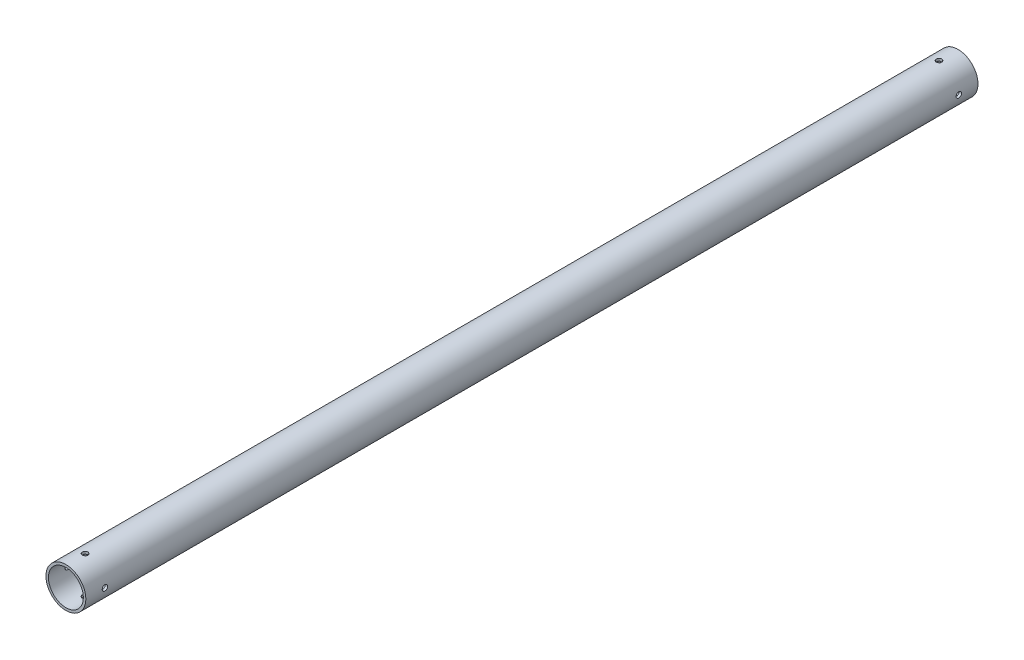
SolidWorks part; units mm, degrees
material "PC High Viscosity"
ref_plane "Front Plane" through (0, 0, 0) normal (0, 0, 1) x (1, 0, 0)
ref_plane "Top Plane" through (0, 0, 0) normal (0, 1, 0) x (1, 0, 0)
ref_plane "Right Plane" through (0, 0, 0) normal (1, 0, 0) x (0, 0, -1)
sketch "Sketch2" plane through (0, 0, 0) normal (0, 0, 1) x (1, 0, 0)
  circle A0 centre (0, 0) radius 11.1125
  circle A1 centre (0, 0) radius 12.7
  dimension "D1" = 25.4
  dimension "D2" = 1.5875
extrude "Boss-Extrude1" add sketch "Sketch2" along normal mid plane 568.4738
sketch "Sketch3" plane through (0, 0, 0) normal (0, 1, 0) x (1, 0, 0)
  line L0 (-12.7, -284.2369) -> (12.7, -284.2369) construction
  line L1 (-55, 0) -> (55, 0) construction
  circle A0 centre (0, -272.0449) radius 1.7526
  circle A1 centre (0, 272.0449) radius 1.7526
  dimension "D1" = 3.5052
  dimension "D2" = 12.192
extrude "Cut-Extrude1" cut sketch "Sketch3" against normal through all both and the other way through all
sketch "Sketch4" plane through (0, 0, 0) normal (1, 0, 0) x (0, 0, -1)
  line L0 (-284.2369, 12.7) -> (-284.2369, -12.7) construction
  line L1 (0, 55) -> (0, -55) construction
  circle A0 centre (-272.0449, 0) radius 1.7526
  circle A1 centre (272.0449, 0) radius 1.7526
  dimension "D1" = 3.5052
  dimension "D2" = 12.192
extrude "Cut-Extrude2" cut sketch "Sketch4" against normal through all both and the other way through all
